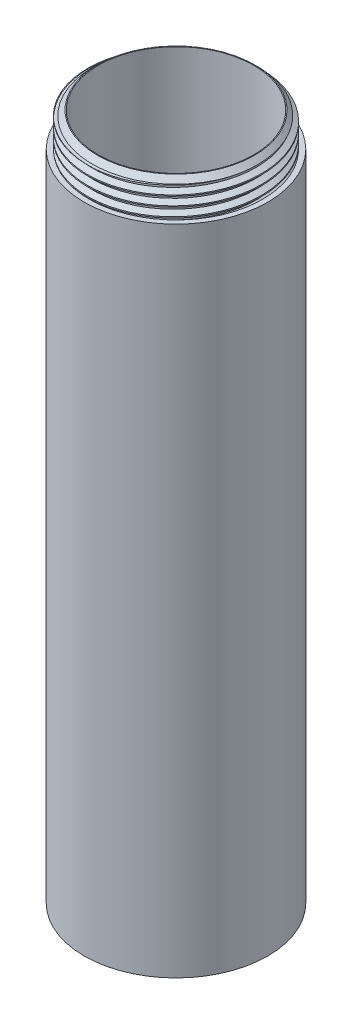
SolidWorks part; units mm, degrees
ref_plane "Front Plane" through (0, 0, 0) normal (0, 0, 1) x (1, 0, 0)
ref_plane "Top Plane" through (0, 0, 0) normal (0, 1, 0) x (1, 0, 0)
ref_plane "Right Plane" through (0, 0, 0) normal (1, 0, 0) x (0, 0, -1)
sketch "Sketch1" plane through (0, 0, 0) normal (0, 1, 0) x (1, 0, 0)
  circle A0 centre (0, 0) radius 17.4625
  circle A1 centre (0, 0) radius 20.6375
  dimension "D1" = 34.925
  dimension "D2" = 3.175
extrude "Boss-Extrude1" add sketch "Sketch1" along normal blind 152.4
sketch "Sketch2" plane through (0, 0, 0) normal (0, -1, 0) x (-1, 0, 0)
  circle A0 centre (0, 0) radius 20.6375
  circle A1 centre (0, 0) radius 20.6375 construction
extrude "Boss-Extrude2" add sketch "Sketch2" along normal blind 2
sketch "Sketch13" plane through (0, 152.4, 0) normal (0, 1, 0) x (1, 0, 0)
  line L0 (-19.4945, 0) -> (-17.4625, 0) construction
  circle A0 centre (0, 0) radius 20.6375
  circle A1 centre (0, 0) radius 19.4945
  circle A2 centre (0, 0) radius 17.4625 construction
  circle A3 centre (0, 0) radius 20.6375 construction
  dimension "D1" = 2.032
extrude "Cut-Extrude1" cut sketch "Sketch13" against normal blind 7.62
thread "Thread1" pitch 2.1167 method cut profile "Thread Profile1" start angle 0, offset 2.54, length 0, pitch 2.1167, diameter 38.989
ref_plane "Plane1" through (-19.4945, 154.94, 0) normal (0, 0, 1) x (-1, 0, 0)
sketch "Thread Profile1" plane through (-19.4945, 154.94, 0) normal (0, 0, 1) x (-1, 0, 0)
  line L0 (0, 0) -> (0, 2.1167) construction
  line L11 (0, 0) -> (0, 1.8521)
  line L12 (0, 1.8521) -> (-1.1457, 1.1906)
  line L13 (-1.1457, 1.1906) -> (-1.1457, 0.6615)
  line L15 (-1.1457, 0.6615) -> (0, 0)
  line L17 (-1.1457, 0.926) -> (0, 0.926) construction
  point P2 (0, 0)
  dimension "Pitch" = 2.1167
  dimension "Profile_Angle" = 60
  dimension "Profile_Land" = 0.5292
  dimension "Profile_Height" = 1.1457
sketch "Sketch16" plane through (0, 0, 0) normal (0, 0, 1) x (1, 0, 0)
  line L0 (0, 0) -> (0, 156.9021) construction
  line L1 (-16.51, 153.543) -> (-18.796, 151.257)
  line L2 (-18.796, 151.257) -> (-21.615, 151.257)
  line L3 (-21.615, 151.257) -> (-21.615, 153.543)
  line L4 (-21.615, 153.543) -> (-16.51, 153.543)
  line L6 (20.6375, 144.78) -> (-20.6375, 144.78) construction
  point P8 (-18.5569, 151.5776)
  point P9 (-19.7511, 150.839)
  point P10 (-20.4921, 150.6018)
  point P11 (-18.5387, 151.5281)
  point P12 (-13.6232, 155.3323)
  point P13 (-19.6795, 152.3508)
  point P14 (-20.443, 150.4883)
  point P15 (-8.2041, 161.6834)
  point P16 (-31.1508, 161.5148)
  point P17 (-16.6166, 153.5559)
  point P18 (0, 0)
  point P19 (-21.615, 151.2764)
  dimension "D1" = 45
  dimension "D2" = 16.51
  dimension "D3" = 2.286
  dimension "D4" = 6.477
revolve "Cut-Revolve1" cut sketch "Sketch16" angle 360 about L0
